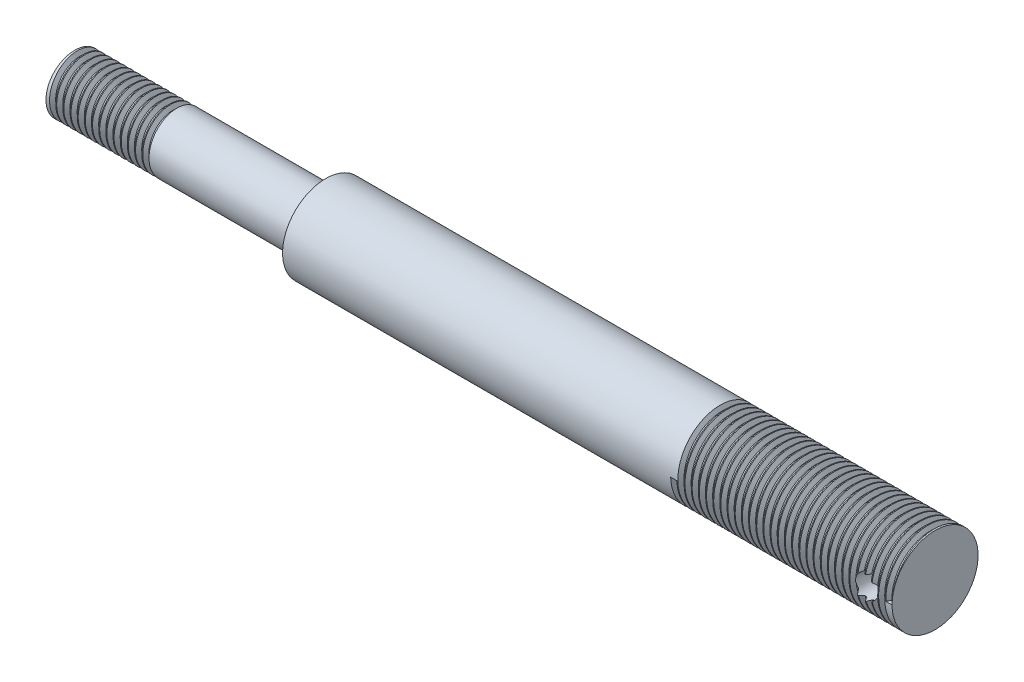
SolidWorks part; units mm, degrees
material "Gray Cast Iron"
ref_plane "Front Plane" through (0, 0, 0) normal (0, 0, 1) x (1, 0, 0)
ref_plane "Top Plane" through (0, 0, 0) normal (0, 1, 0) x (1, 0, 0)
ref_plane "Right Plane" through (0, 0, 0) normal (1, 0, 0) x (0, 0, -1)
sketch "Sketch1" plane through (0, 0, 0) normal (1, 0, 0) x (0, 0, -1)
  circle A0 centre (0, 0) radius 6
  dimension "D1" = 12
extrude "Boss-Extrude1" add sketch "Sketch1" against normal blind 85
sketch "Sketch2" plane through (-85, 0, 0) normal (-1, 0, 0) x (0, 0, 1)
  circle A0 centre (0, 0) radius 4
  dimension "D1" = 8
extrude "Boss-Extrude2" add sketch "Sketch2" along normal blind 35
sketch "Sketch7" plane through (0, 0, 0) normal (0, 0, 1) x (1, 0, 0)
  line L0 (-1000, 0) -> (49000, 0) construction
  line L2 (0, -6) -> (0, 6) construction
  circle A2 centre (-4, 0) radius 1.6
  dimension "D1" = 4
  dimension "D2" = 3.2
extrude "Cut-Extrude3" cut sketch "Sketch7" against normal through all both and the other way through all contours A2
thread "Thread1" pitch 1 method cut profile "Thread Profile1" start angle 0, offset 0, length 30, pitch 1, diameter 12
ref_plane "Plane1" through (0, 0, 6) normal (0, -1, 0) x (0, 0, 1)
sketch "Thread Profile1" plane through (0, 0, 6) normal (0, -1, 0) x (0, 0, 1)
  line L0 (0, 0) -> (0, 1) construction
  line L11 (0, 0) -> (0, 0.875)
  line L12 (0, 0.875) -> (-0.5413, 0.5625)
  line L13 (-0.5413, 0.5625) -> (-0.5413, 0.3125)
  line L15 (-0.5413, 0.3125) -> (0, 0)
  line L17 (-0.5413, 0.4375) -> (0, 0.4375) construction
  point P2 (0, 0)
  dimension "Pitch" = 1
  dimension "Profile_Angle" = 60
  dimension "Profile_Land" = 0.25
  dimension "Profile_Height" = 0.5413
thread "Thread2" pitch 1 method cut profile "Thread Profile2" start angle 0, offset 0, length 14, pitch 1, diameter 8
ref_plane "Plane2" through (-120, 0, -4) normal (0, -1, 0) x (0, 0, -1)
sketch "Thread Profile2" plane through (-120, 0, -4) normal (0, -1, 0) x (0, 0, -1)
  line L0 (0, 0) -> (0, 1) construction
  line L11 (0, 0) -> (0, 0.875)
  line L12 (0, 0.875) -> (-0.5413, 0.5625)
  line L13 (-0.5413, 0.5625) -> (-0.5413, 0.3125)
  line L15 (-0.5413, 0.3125) -> (0, 0)
  line L17 (-0.5413, 0.4375) -> (0, 0.4375) construction
  point P2 (0, 0)
  dimension "Pitch" = 1
  dimension "Profile_Angle" = 60
  dimension "Profile_Land" = 0.25
  dimension "Profile_Height" = 0.5413
